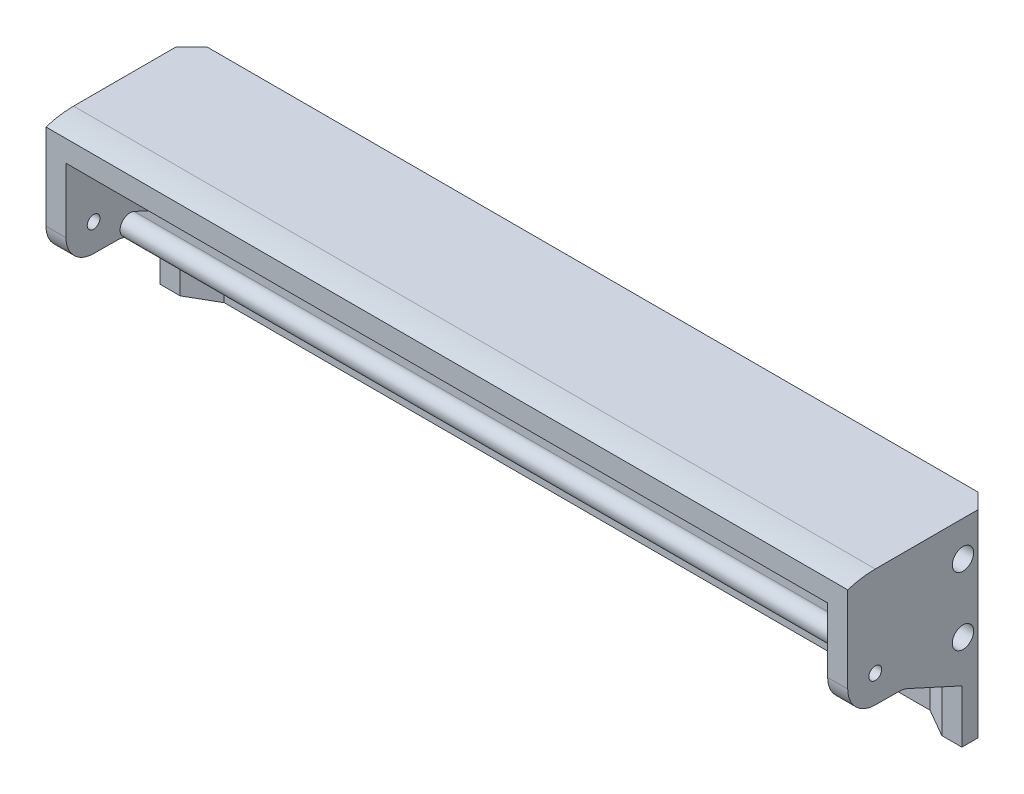
SolidWorks part; units mm, degrees
material "PET"
ref_plane "Front Plane" through (0, 0, 0) normal (0, 0, 1) x (1, 0, 0)
ref_plane "Top Plane" through (0, 0, 0) normal (0, 1, 0) x (1, 0, 0)
ref_plane "Right Plane" through (0, 0, 0) normal (1, 0, 0) x (0, 0, -1)
sketch "Sketch1" plane through (0, 0, 0) normal (1, 0, 0) x (0, 0, -1)
  line L3 (-34.036, 0) -> (42.164, 0) construction
  line L4 (-34.036, 0) -> (-34.036, 28.956) construction
  line L5 (-34.036, 28.956) -> (42.164, 28.956) construction
  line L11 (19.8576, 39.1492) -> (42.164, 28.956)
  line L12 (42.164, 28.956) -> (42.164, 0) construction
  line L13 (42.164, 28.956) -> (42.164, 14.4653)
  line L14 (46.99, 14.4653) -> (46.99, 77.089)
  line L15 (42.164, 14.4653) -> (46.99, 14.4653)
  line L16 (0.889, 48.514) -> (0.889, 75.7224)
  line L17 (9.5529, 39.783) -> (17.2674, 39.7235)
  line L18 (9.6202, 77.089) -> (46.99, 77.089)
  line L20 (37.4015, 44.4881) -> (69.4015, 44.4881) construction
  line L21 (22.4969, 44.9248) -> (42.164, 35.9376) construction
  circle A0 centre (9.6202, 48.514) radius 2.0193
  arc A2 (0.889, 48.514) -> (9.5529, 39.783) centre (9.6202, 48.514) ccw
  circle A7 centre (21.1772, 42.037) radius 3.175 construction
  arc A8 (19.8576, 39.1492) -> (17.2674, 39.7235) centre (17.2184, 33.3737) ccw
  arc A9 (9.6202, 77.089) -> (0.889, 75.7224) centre (9.6202, 48.514) ccw
  circle A12 centre (37.4015, 65.9765) radius 3.3782
  circle A14 centre (37.4015, 44.4881) radius 3.3782
  point P9 (0.889, 48.514)
  point P25 (0, 0)
  dimension "D2" = 4.0386
  dimension "D5" = 0.889
  dimension "D6" = 17.4625
  dimension "D8" = 6.35
  dimension "D13" = 6.35
  dimension "D14" = 28.575
  dimension "D15" = 9.5885
  dimension "D20" = 6.7564
  dimension "D19" = 11.1125
  dimension "D3" = 42.037
  dimension "D4" = 48.514
  dimension "D7" = 11.557
  dimension "D9" = 28.956
  dimension "D10" = 76.2
  dimension "D11" = 41.275
  dimension "D12" = 14.4653
  dimension "D16" = 4.826
  dimension "D17" = 5.7976
  dimension "D18" = 44.4881
  dimension "D21" = 32
  dimension "D22" = 36.5125
  dimension "D23" = 21.4884
extrude "Boss-Extrude1" add sketch "Sketch1" against normal blind 6.35 contours A2 A0 A7 | L13 L15 L14 A2 region at (0, 55.1501, -25.809)
sketch "Sketch2" plane through (0, 0, 0) normal (1, 0, 0) x (0, 0, -1)
  line L0 (22.4969, 44.9248) -> (42.164, 35.9376)
  line L1 (42.164, 35.9376) -> (42.164, 70.739)
  line L2 (42.164, 70.739) -> (40.64, 70.739)
  line L3 (40.64, 70.739) -> (9.6202, 70.739)
  line L4 (46.99, 14.4653) -> (46.99, 77.089)
  line L5 (46.99, 77.089) -> (9.6202, 77.089)
  line L6 (46.99, 14.4653) -> (46.99, 77.089)
  line L7 (46.99, 77.089) -> (9.6202, 77.089)
  line L8 (0.889, 48.514) -> (0.889, 75.7224) construction
  line L9 (0.889, 68.9521) -> (0.889, 75.7224)
  line L10 (46.99, 14.4653) -> (42.164, 14.4653)
  line L11 (42.164, 14.4653) -> (42.164, 28.956)
  line L12 (19.8576, 39.1492) -> (42.164, 28.956)
  line L13 (40.64, 14.4653) -> (40.64, 70.739) construction
  circle A0 centre (21.1772, 42.037) radius 3.175
  arc A1 (9.6202, 70.739) -> (2.8293, 69.6761) centre (9.6202, 48.514) ccw
  arc A2 (9.6202, 77.089) -> (0.889, 75.7224) centre (9.6202, 48.514) ccw
  arc A3 (9.6202, 77.089) -> (0.889, 75.7224) centre (9.6202, 48.514) ccw
  arc A4 (2.8293, 69.6761) -> (0.889, 68.9521) centre (9.6202, 48.514) ccw
  circle A5 centre (21.1772, 42.037) radius 3.175 construction
  line M17 (46.99, 77.089) -> (9.6202, 77.089)
  arc M18 (9.6202, 77.089) -> (0.889, 75.7224) centre (9.6202, 48.514) ccw
  line M19 (0.889, 75.7224) -> (0.889, 48.514)
  line M23 (19.8576, 39.1492) -> (42.164, 28.956)
  line M24 (42.164, 28.956) -> (42.164, 14.4653)
  line M25 (42.164, 14.4653) -> (46.99, 14.4653)
  line M26 (46.99, 14.4653) -> (46.99, 77.089)
  dimension "D1" = 0
  dimension "D2" = 6.35
extrude "Boss-Extrude2" add sketch "Sketch2" along normal blind 120.65 contours A4 A1 L3 M24 M25 M26 M17 M18 M19 | A0 L0 M23 | A0 region at (0, 39.7239, -32.0072) region at (0, 42.037, -21.1772)
sketch "Sketch5" plane through (0, 14.4653, 0) normal (0, -1, 0) x (1, 0, 0)
  line L0 (17.2, -46.99) -> (0, -37.0596)
  line L1 (-6.35, -46.99) -> (120.65, -46.99) construction
  line L2 (-6.35, -37.0596) -> (-6.35, -46.99)
  line L3 (-6.35, -46.99) -> (17.2, -46.99)
  line L4 (4.5, -46.99) -> (-6.35, -40.7257)
  line L5 (-6.35, -37.0596) -> (0, -37.0596)
  line M6 (120.65, -42.164) -> (-6.35, -42.164)
  dimension "D1" = 30
  dimension "D2" = 23.55
  dimension "D3" = 6.35
  dimension "D4" = 9.9304
extrude "Boss-Extrude3" add sketch "Sketch5" against normal up to surface (14.4907 mm away) contours L5 L2 L4 L0 M6 | L4 L2 M6 region at (-0.4987, 14.4653, -39.9029) region at (-5.5196, 14.4653, -41.6846) up to face at (45.72, 35.0719, -28.7802)
sketch "Sketch6" plane through (-6.35, 0, 0) normal (-1, 0, 0) x (0, 0, 1)
  line L0 (-26.9183, 86.3416) -> (-36.171, 77.089)
  line L1 (-9.6202, 77.089) -> (-46.99, 77.089) construction
  line L2 (-16.0782, 81.8515) -> (-16.0782, 77.089)
  line L3 (-36.171, 77.089) -> (-16.0782, 77.089)
  circle A0 centre (-22.4282, 81.8515) radius 3.3782
  circle A1 centre (-37.4015, 44.4881) radius 3.3782 construction
  arc A2 (-16.0782, 81.8515) -> (-26.9183, 86.3416) centre (-22.4282, 81.8515) ccw
  point P3 (-37.4015, 44.4881)
  dimension "D1" = 14.9733
  dimension "D3" = 37.3634
  dimension "D4" = 6.35
  dimension "D2" = 4.7625
  dimension "D5" = 45
extrude "Boss-Extrude4" [suppressed] add sketch "Sketch6" against normal up to surface (6.35 mm away) up to face at (0, 44.4881, -40.7797)
fillet "Fillet2" [suppressed] radius 3.175
mirror "Mirror1" about plane through (120.65, 0, 0) normal (1, 0, 0) of bodies 106 103
sketch "Sketch4" plane through (0, 0, -46.99) normal (0, 0, -1) x (-1, 0, 0)
  line L0 (-120.65, -112.5347) -> (-278.9619, 45.7771) construction
  line L1 (-120.65, -112.5347) -> (37.6619, 45.7772) construction
  line L2 (-278.9619, 45.7771) -> (-120.65, 204.089) construction
  line L3 (37.6619, 45.7772) -> (-120.65, 204.089) construction
  line L4 (-120.65, -112.5347) -> (-120.65, 204.089) construction
  line L5 (-278.9619, 45.7771) -> (37.6619, 45.7772) construction
  point P1 (-120.65, 45.7771)
  dimension "D1" = 223.8868
chamfer "Chamfer1" distance 4.826 angle 45 2 edges at (247.65, 45.7771, -46.99) (-6.35, 45.7771, -46.99)
